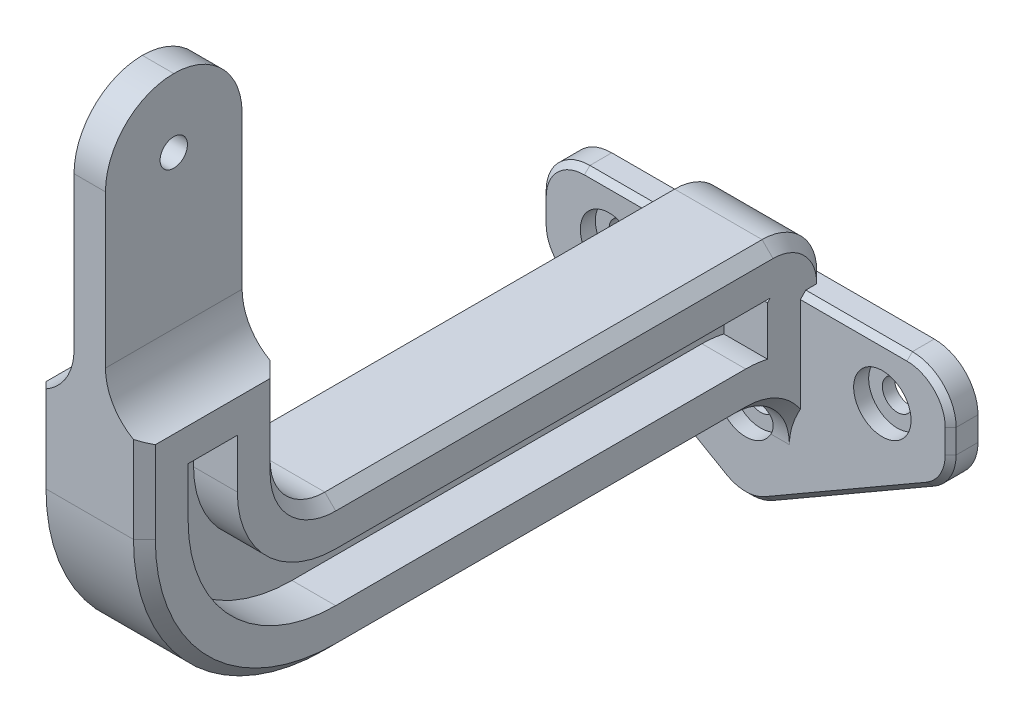
SolidWorks part; units mm, degrees
ref_plane "Front Plane" through (0, 0, 0) normal (0, 0, 1) x (1, 0, 0)
ref_plane "Top Plane" through (0, 0, 0) normal (0, 1, 0) x (1, 0, 0)
ref_plane "Right Plane" through (0, 0, 0) normal (1, 0, 0) x (0, 0, -1)
other "1"
sketch "Sketch2" plane through (0, 0, 0) normal (0, 0, 1) x (1, 0, 0)
  line L0 (-37.5, 28.0006) -> (0, 6.35)
  line L1 (0, 6.35) -> (37.5, 28.0006)
  line L2 (37.5, 28.0006) -> (37.5, 45)
  line L3 (37.5, 45) -> (-37.5, 45)
  line L4 (-37.5, 45) -> (-37.5, 28.0006)
  line L5 (0, 6.35) -> (0, 45) construction
  dimension "D1" = 6.35
  dimension "D2" = 45
  dimension "D3" = 75
  dimension "D4" = 120
extrude "Boss-Extrude1" add sketch "Sketch2" along normal blind 5 contours L3 L4 L0 L1 L2
ref_plane "Plane1" through (37.5, 45, 0) normal (0, 0, -1) x (-1, 0, 0)
fillet "Fillet1" radius 8 5 edges at (-37.5, 45, 2.5) (-37.5, 28.0006, 2.5) (0, 6.35, 2.5) (37.5, 28.0006, 2.5) (37.5, 45, 2.5)
hole_wizard "CBORE for M5 SBHCS1" positions "Sketch5" profile "Sketch6" counterbore size "M5" standard "ANSI Metric"
sketch "Sketch5" plane through (0, 0, 5) normal (0, 0, 1) x (1, 0, 0)
  point P0 (-25, 35)
  point P3 (0, 22.5)
  point P6 (25, 35)
sketch "Sketch6" plane through (-25, 35, 5) normal (1, 0, 0) x (0, -1, 0)
  line L0 (0, 0) -> (0, 11.6524)
  line L1 (0, 11.6524) -> (2.75, 10)
  line L2 (2.75, 10) -> (2.75, 2.75)
  line L3 (2.75, 2.75) -> (5.25, 2.75)
  line L4 (5.25, 2.75) -> (5.25, 0)
  line L5 (5.25, 0) -> (0, 0)
  line L10 (0, 11.6524) -> (-2.75, 10) construction
  line L11 (0, -6.35) -> (0, 107.95) construction
  dimension "Hole Dia." = 5.5
  dimension "Hole Depth" = 10
  dimension "C'Bore Dia." = 10.5
  dimension "C'Bore Depth" = 2.75
  dimension "Drill Angle" = 118
sketch "Sketch7" plane through (0, 0, 5) normal (0, 0, 1) x (1, 0, 0)
  line L0 (0, 80) -> (0, 0) construction
  line L1 (-10, 130) -> (10, 130)
  line L2 (-10, 130) -> (-10, 30)
  line L3 (-10, 30) -> (10, 30)
  line L4 (10, 130) -> (10, 30)
  line L5 (-10, 130) -> (10, 30) construction
  line L6 (-10, 30) -> (10, 130) construction
  point P0 (0, 80)
  dimension "D1" = 80
  dimension "D2" = 100
  dimension "D3" = 20
extrude "Boss-Extrude2" add sketch "Sketch7" along normal blind 120
sketch "Sketch8" plane through (10, 0, 0) normal (1, 0, 0) x (0, 0, -1)
  line L0 (-125, 30) -> (-125, 130) construction
  line L1 (90, 205) -> (-100, 205)
  line L2 (90, 205) -> (90, 55)
  line L3 (90, 55) -> (-100, 55)
  line L4 (-100, 205) -> (-100, 55)
  line L5 (90, 205) -> (-100, 55) construction
  line L6 (90, 55) -> (-100, 205) construction
  line L7 (-125, 30) -> (-5, 30) construction
  point P0 (-5, 130)
  dimension "D1" = 25
  dimension "D2" = 25
extrude "Cut-Extrude1" cut sketch "Sketch8" against normal blind 72
fillet "Fillet2" radius 12.5 2 edges at (0, 130, 100) (0, 130, 125)
sketch "Sketch9" plane through (0, 0, 125) normal (0, 0, 1) x (1, 0, 0)
  line L1 (17.125, 180) -> (2.875, 180)
  line L2 (17.125, 180) -> (17.125, 80)
  line L3 (17.125, 80) -> (2.875, 80)
  line L4 (2.875, 180) -> (2.875, 80)
  line L5 (17.125, 180) -> (2.875, 80) construction
  line L6 (17.125, 80) -> (2.875, 180) construction
  line L7 (-17.125, 180) -> (-2.875, 180)
  line L8 (-17.125, 180) -> (-17.125, 80)
  line L9 (-17.125, 80) -> (-2.875, 80)
  line L10 (-2.875, 180) -> (-2.875, 80)
  line L11 (-17.125, 180) -> (-2.875, 80) construction
  line L12 (-17.125, 80) -> (-2.875, 180) construction
  point P0 (10, 130)
  point P5 (-10, 130)
  dimension "D1" = 5.75
  dimension "D2" = 50
extrude "Cut-Extrude2" cut sketch "Sketch9" against normal blind 72
sketch "Sketch10" plane through (2.875, 0, 0) normal (1, 0, 0) x (0, 0, -1)
  circle A0 centre (-112.5, 117.5) radius 2.5
  dimension "D1" = 5
extrude "Cut-Extrude3" cut sketch "Sketch10" against normal blind 72
fillet "Fillet3" radius 10 2 edges at (-2.875, 80, 112.5) (2.875, 80, 112.5)
fillet "Fillet4" radius 10 1 edges at (0, 55, 100)
fillet "Fillet5" radius 35 1 edges at (0, 30, 125)
fillet "Fillet6" radius 10 1 edges at (0, 30, 5)
sketch "Sketch12" plane through (0, 0, 5) normal (0, 0, -1) x (-1, 0, 0)
  line L4 (10, 45) -> (10, 55)
  line L5 (10, 55) -> (-10, 55)
  line L6 (-10, 55) -> (-10, 45)
  line L8 (10, 45) -> (10, 55)
  line L10 (-10, 55) -> (-10, 45)
  line L12 (10, 55) -> (-10, 55)
  line L14 (-10, 45) -> (10, 45)
  line L15 (-10, 45) -> (10, 45)
  dimension "D1" = 0
extrude "Boss-Extrude3" add sketch "Sketch12" along normal blind 5
fillet "Fillet7" radius 10 1 edges at (0, 55, 0)
chamfer "Chamfer1" distance 2 angle 45 16 edges at (-10, 72.5, 100) (-10, 57.9289, 97.0711) (-10, 55, 50) (10, 72.5, 100) (10, 57.9289, 97.0711) (10, 55, 50) (-10, 27.0711, 7.9289) (-10, 30, 52.5) (-10, 40.2513, 114.7487) (-10, 72.5, 125) (10, 27.0711, 7.9289) (10, 30, 52.5) (10, 40.2513, 114.7487) (10, 72.5, 125) (-10, 52.0711, 2.9289) (10, 52.0711, 2.9289)
chamfer "Chamfer2" distance 1 angle 45 11 edges at (-19.75, 45, 5) (-35.1569, 42.6569, 5) (-37.5, 34.8097, 5) (-36.4282, 28.6194, 5) (-18.75, 17.1753, 5) (0, 7.5876, 5) (18.75, 17.1753, 5) (36.4282, 28.6194, 5) (37.5, 34.8097, 5) (35.1569, 42.6569, 5) (19.75, 45, 5)
sketch "Sketch13" plane through (10, 0, 0) normal (1, 0, 0) x (0, 0, -1)
  line L8 (-11, 37.5499) -> (-11, 46.4853)
  line L12 (-108, 65) -> (-108, 74)
  line L14 (-108, 65) -> (-108, 74)
  line L17 (-11, 37.5499) -> (-11, 46.4853)
  line L18 (-117, 74) -> (-117, 65)
  line L19 (-90, 38) -> (-15, 38)
  line L24 (-117, 74) -> (-117, 65)
  line L25 (-90, 38) -> (-15, 38)
  line L28 (-108, 74) -> (-117, 74)
  line L29 (-108, 74) -> (-117, 74)
  line L32 (-10.4853, 47) -> (-90, 47)
  line L33 (-10.4853, 47) -> (-90, 47)
  line L35 (-11, 46.4853) -> (-10.4853, 47)
  line L36 (-11, 46.4853) -> (-10.4853, 47)
  arc A6 (-108, 65) -> (-90, 47) centre (-90, 65) ccw
  arc A9 (-117, 65) -> (-90, 38) centre (-90, 65) ccw
  arc A11 (-108, 65) -> (-90, 47) centre (-90, 65) ccw
  arc A13 (-117, 65) -> (-90, 38) centre (-90, 65) ccw
  arc A16 (-11, 37.5499) -> (-15, 38) centre (-15, 20) ccw
  arc A17 (-11, 37.5499) -> (-15, 38) centre (-15, 20) ccw
  dimension "D1" = 6
extrude "Cut-Extrude4" cut sketch "Sketch13" against normal blind 8
mirror "Mirror1" about plane through (0, 0, 0) normal (1, 0, 0) of "Cut-Extrude4"
